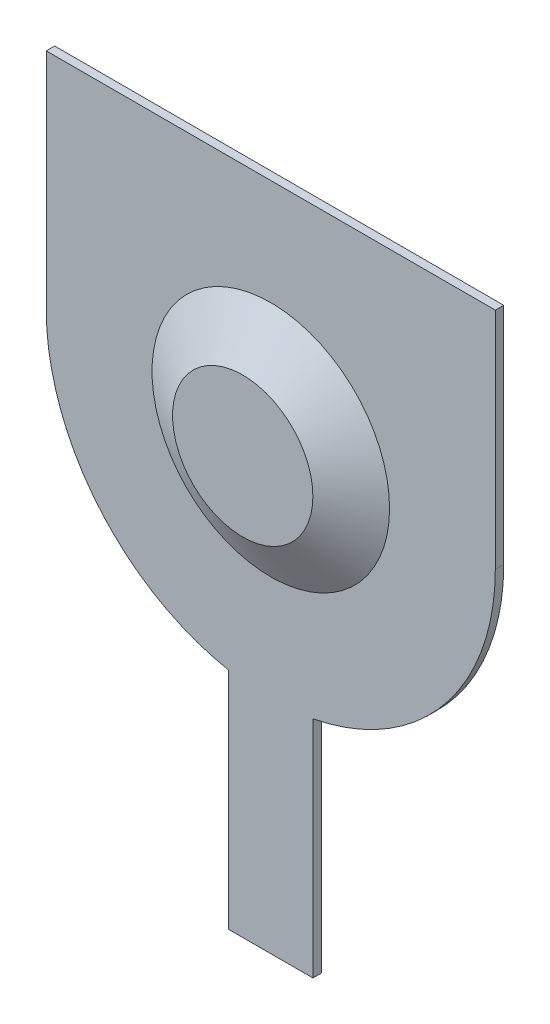
SolidWorks part; units mm, degrees
ref_plane "前视基准面" through (0, 0, 0) normal (0, 0, 1) x (1, 0, 0)
ref_plane "上视基准面" through (0, 0, 0) normal (0, 1, 0) x (1, 0, 0)
ref_plane "右视基准面" through (0, 0, 0) normal (1, 0, 0) x (0, 0, -1)
other "Configuration Table"
sketch "草图1" plane through (0, 0, 0) normal (0, 0, 1) x (1, 0, 0)
  line L0 (-8, 0) -> (-8, 8)
  line L1 (-8, 8) -> (8, 8)
  line L2 (8, 8) -> (8, 0)
  line L3 (0, 0) -> (0, -15.8581) construction
  line L5 (-1.5, -7.8581) -> (-1.5, -15.8581)
  line L6 (-1.5, -15.8581) -> (1.5, -15.8581)
  line L7 (1.5, -7.8581) -> (1.5, -15.8581)
  arc A0 (-8, 0) -> (-1.5, -7.8581) centre (0, 0) ccw
  arc A1 (1.5, -7.8581) -> (8, 0) centre (0, 0) ccw
  point P10 (0, -15.8581)
  dimension "D1" = 8
  dimension "D2" = 3
  dimension "D3" = 8
extrude "凸台-拉伸1" add sketch "草图1" along normal blind 0.3 contours L0 L1 L2 A1 L7 L6 L5 A0
sketch "草图2" plane through (0, 0, 0.3) normal (0, 0, 1) x (1, 0, 0)
  circle A0 centre (0, 0) radius 2.5
  dimension "D1" = 5
extrude "凸台-拉伸2" add sketch "草图2" along normal blind 1
chamfer "倒角1" distance 1 angle 60 1 edges at (2.5, 0, 0.3) first distance on face at (2.5, 0, 1.3)
